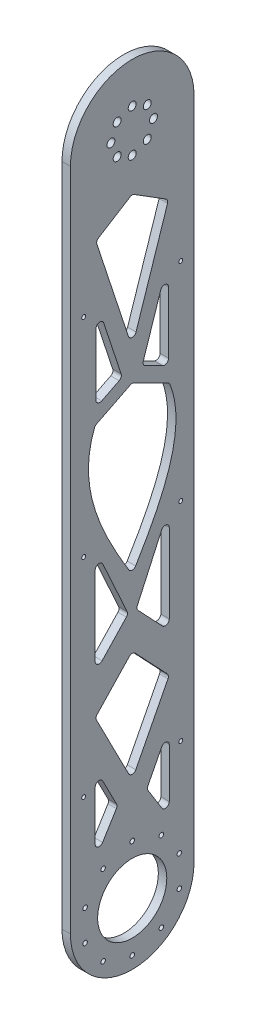
SolidWorks part; units mm, degrees
material "1060 Alloy"
ref_plane "Front Plane" through (0, 0, 0) normal (0, 0, 1) x (1, 0, 0)
ref_plane "Top Plane" through (0, 0, 0) normal (0, 1, 0) x (1, 0, 0)
ref_plane "Right Plane" through (0, 0, 0) normal (1, 0, 0) x (0, 0, -1)
sketch "Sketch1" plane through (0, 0, 0) normal (1, 0, 0) x (0, -1, 0)
  line L0 (0, 0) -> (500, 0) construction
  line L1 (0, 46.5) -> (500, 46.5)
  line L2 (0, -46.5) -> (500, -46.5)
  arc A0 (0, 46.5) -> (0, -46.5) centre (0, 0) ccw
  arc A1 (500, -46.5) -> (500, 46.5) centre (500, 0) ccw
  circle A2 centre (0, 0) radius 16 construction
  circle A3 centre (-16, 0) radius 3
  circle A4 centre (-11.3137, 11.3137) radius 3
  circle A5 centre (0, 16) radius 3
  circle A6 centre (11.3137, 11.3137) radius 3
  circle A7 centre (16, 0) radius 3
  circle A8 centre (11.3137, -11.3137) radius 3
  circle A27 centre (500, 0) radius 37.25 construction
  circle A28 centre (537.25, 0) radius 1.7
  circle A29 centre (500, 0) radius 37.25 construction
  circle A30 centre (537.25, 0) radius 1.7
  circle A31 centre (530.1359, -21.895) radius 1.7
  circle A32 centre (511.5109, -35.4269) radius 1.7
  circle A33 centre (488.4891, -35.4269) radius 1.7
  circle A34 centre (469.8641, -21.895) radius 1.7
  circle A35 centre (462.75, 0) radius 1.7
  circle A36 centre (469.8641, 21.895) radius 1.7
  circle A37 centre (488.4891, 35.4269) radius 1.7
  circle A38 centre (511.5109, 35.4269) radius 1.7
  circle A39 centre (530.1359, 21.895) radius 1.7
  circle A40 centre (500, 0) radius 26
  circle A41 centre (0, -16) radius 3
  circle A42 centre (-11.3137, -11.3137) radius 3
  point P3 (250, 0)
  point P25 (0, 0)
  point P52 (500, 0)
  point P61 (500, 0)
  dimension "D3" = 32
  dimension "D4" = 6
  dimension "D2" = 74.5
  dimension "D7" = 3.4
  dimension "D8" = 3.4
  dimension "D10" = 52
  dimension "D6" = 46.5
  dimension "D1" = 500
  dimension "D5" = 8
  dimension "D9" = 10
extrude "Boss-Extrude1" add sketch "Sketch1" along normal blind 6.35 contours L2 A1 L1 A0 A40 A39 A38 A37 A36 A35 A34 A33 A32 A31 A28 A8 A7 A6 A5 A4 A3 region at (0, -240.225, 0)
ref_axis "Axis1" through (6.35, -500, 0) along (-1, 0, 0)
sketch "Sketch3" plane through (6.35, 0, 0) normal (1, 0, 0) x (0, 0, -1)
  line L0 (0, -500) -> (0, 0) construction
  line L1 (0, -422.848) -> (27.8582, -368.6328)
  line L2 (0, -422.848) -> (-27.8582, -368.6328)
  line L3 (-27.8582, -368.6328) -> (0, -339.1393)
  line L4 (0, -339.1393) -> (27.8582, -368.6328)
  line L5 (0, -41.3687) -> (-27.3129, -58.4352)
  line L6 (-27.3129, -58.4352) -> (0, -141.249)
  line L7 (0, -141.249) -> (27.3129, -58.4352)
  line L8 (27.3129, -58.4352) -> (0, -41.3687)
  line L9 (3, -313.1891) -> (27.8582, -339.5065)
  line L10 (27.8582, -339.5065) -> (27.8582, -258.646)
  line L11 (27.8582, -258.646) -> (3, -313.1891)
  line L12 (-27.8582, -339.5065) -> (-27.8582, -258.646)
  line L13 (-3, -313.1891) -> (-27.8582, -339.5065)
  line L14 (-27.8582, -258.646) -> (-3, -313.1891)
  line L15 (-27.8582, -401.4529) -> (-11, -434.2608)
  line L16 (-11, -434.2608) -> (-27.8582, -461.4818)
  line L17 (-27.8582, -461.4818) -> (-27.8582, -401.4529)
  line L18 (11, -434.2608) -> (27.8582, -461.4818)
  line L19 (27.8582, -401.4529) -> (11, -434.2608)
  line L20 (27.8582, -461.4818) -> (27.8582, -401.4529)
  line L21 (0, -164.2489) -> (-27.8582, -178.2005)
  line L22 (0, -164.2489) -> (27.8582, -178.2005)
  line L23 (7.5, -156.821) -> (27.3129, -96.7475)
  line L24 (27.3129, -96.7475) -> (27.3129, -166.7434)
  line L25 (27.3129, -166.7434) -> (7.5, -156.821)
  line L26 (-27.3129, -96.7475) -> (-27.3129, -166.7434)
  line L27 (-7.5, -156.821) -> (-27.3129, -96.7475)
  line L28 (-27.3129, -166.7434) -> (-7.5, -156.821)
  spline S0 degree 3 poles (-27.8582, -178.2005) (-43.7791, -216.0933) (-18.6166, -258.2761) (0, -289.085) knots 0 0 0 0 1 1 1 1
  spline S1 degree 3 poles (27.8582, -178.2005) (43.7791, -216.0933) (18.6166, -258.2761) (0, -289.085) knots 0 0 0 0 1 1 1 1
  dimension "D1" = 15
  dimension "D2" = 20
  dimension "D3" = 12
  dimension "D4" = 10
  dimension "D5" = 6
  dimension "D6" = 15
  dimension "D7" = 22
extrude "Cut-Extrude1" cut sketch "Sketch3" against normal through all
fillet "Fillet1" radius 3 30 edges at (3.175, -58.4352, -27.3129) (3.175, -41.3687, 0) (3.175, -58.4352, 27.3129) (3.175, -141.249, 0) (3.175, -289.085, 0) (3.175, -164.2489, 0) (3.175, -401.4529, 27.8582) (3.175, -434.2608, 11) (3.175, -461.4818, 27.8582) (3.175, -461.4818, -27.8582) (3.175, -434.2608, -11) (3.175, -401.4529, -27.8582) (3.175, -368.6328, -27.8582) (3.175, -339.1393, 0) (3.175, -368.6328, 27.8582) (3.175, -422.848, 0) (3.175, -313.1891, 3) (3.175, -339.5065, 27.8582) (3.175, -258.646, 27.8582) (3.175, -178.2005, -27.8582) (3.175, -178.2005, 27.8582) (3.175, -339.5065, -27.8582) (3.175, -313.1891, -3) (3.175, -258.646, -27.8582) (3.175, -96.7475, 27.3129) (3.175, -166.7434, 27.3129) (3.175, -156.821, 7.5) (3.175, -166.7434, -27.3129) (3.175, -156.821, -7.5) (3.175, -96.7475, -27.3129)
sketch "Sketch4" plane through (6.35, 0, 0) normal (1, 0, 0) x (0, 0, -1)
  line L0 (0, 46.5) -> (-113.1579, 46.5) construction
  line L1 (-46.5, 0) -> (-46.5, -500) construction
  line L2 (-46.5, -100) -> (46.5, -100) construction
  line L3 (46.5, 0) -> (46.5, -500) construction
  line L4 (-46.5, -106.35) -> (46.5, -106.35) construction
  line L5 (-36.5, -100) -> (-36.5, -106.35) construction
  line L6 (0, 0) -> (0, -106.35) construction
  line L7 (0, -106.35) -> (0, -256.35) construction
  line L8 (0, -256.35) -> (46.5, -256.35) construction
  line L9 (46.5, -262.7) -> (-46.5, -262.7) construction
  line L10 (0, -181.35) -> (46.5, -181.35) construction
  line L11 (0, -262.7) -> (0, -412.7) construction
  line L12 (0, -412.7) -> (46.5, -412.7) construction
  line L13 (0, -337.7) -> (46.5, -337.7) construction
  arc A1 (46.5, 0) -> (-46.5, 0) centre (0, 0) ccw construction
  circle A2 centre (-36.5, -103.175) radius 1.5
  circle A3 centre (36.5, -103.175) radius 1.5
  circle A4 centre (-36.5, -259.525) radius 1.5
  circle A5 centre (36.5, -259.525) radius 1.5
  circle A6 centre (-36.5, -415.875) radius 1.5
  circle A7 centre (36.5, -415.875) radius 1.5
  point P17 (-36.5, -103.175)
  dimension "D1" = 3
  dimension "D2" = 6.35
  dimension "D3" = 10
  dimension "D4" = 146.5
  dimension "D5" = 150
  dimension "D6" = 6.35
  dimension "D7" = 81.35
  dimension "D8" = 150
  dimension "D9" = 81.35
extrude "Cut-Extrude2" cut sketch "Sketch4" against normal through all
equation "\"L1L\"=500"
equation "\"D1@Sketch1\"=\"L1L\""
equation "\"L1Thick\"=6.35"
equation "\"D1@Boss-Extrude1\"=\"L1Thick\""
equation "\"Harm-Drive-Outer\"=74.5"
equation "\"D2@Sketch1\"=\"Harm-Drive-Outer\""
